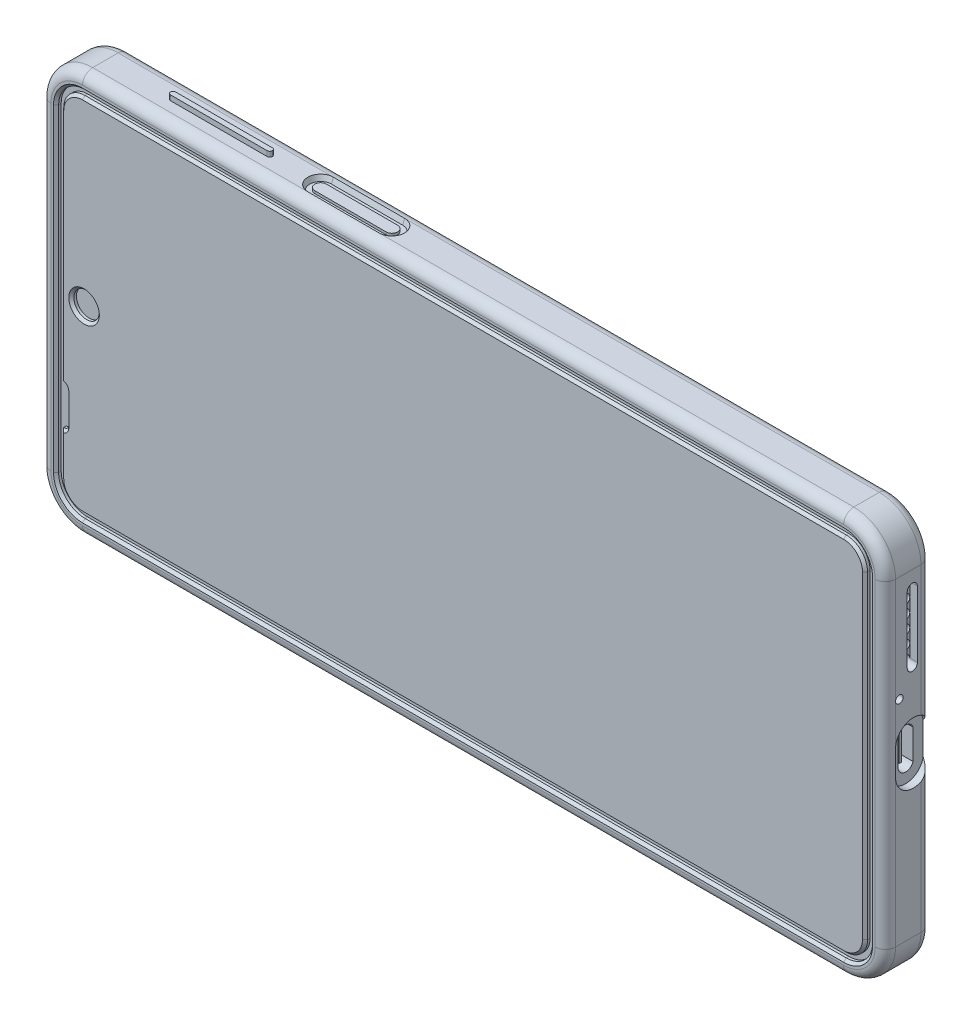
SolidWorks part; units mm, degrees
ref_plane "Front Plane" through (0, 0, 0) normal (0, 0, 1) x (1, 0, 0)
ref_plane "Top Plane" through (0, 0, 0) normal (0, 1, 0) x (1, 0, 0)
ref_plane "Right Plane" through (0, 0, 0) normal (1, 0, 0) x (0, 0, -1)
sketch "Sketch1" plane through (0, 0, 0) normal (0, 0, 1) x (1, 0, 0)
  line L1 (-83, -39.5) -> (83, -39.5)
  line L2 (-83, -39.5) -> (-83, 39.5)
  line L3 (-83, 39.5) -> (83, 39.5)
  line L4 (83, -39.5) -> (83, 39.5)
  line L5 (-83, -39.5) -> (83, 39.5) construction
  line L6 (-83, 39.5) -> (83, -39.5) construction
  point P0 (0, 0)
  dimension "D1" = 79
  dimension "D2" = 166
extrude "Boss-Extrude1" add sketch "Sketch1" along normal blind 9
fillet "Fillet1" radius 2 8 edges at (0, 39.5, 0) (-83, 0, 0) (0, -39.5, 0) (83, 0, 0) (0, -39.5, 9) (-83, 0, 9) (0, 39.5, 9) (83, 0, 9)
fillet "Fillet2" radius 8.2 12 edges at (82.4142, 38.9142, 0.5858) (82.4142, 38.9142, 8.4142) (-82.4142, 38.9142, 0.5858) (-82.4142, 38.9142, 8.4142) (-82.4142, -38.9142, 0.5858) (-82.4142, -38.9142, 8.4142) (82.4142, -38.9142, 0.5858) (82.4142, -38.9142, 8.4142) (83, -39.5, 4.5) (-83, -39.5, 4.5) (-83, 39.5, 4.5) (83, 39.5, 4.5)
sketch "Sketch2" plane through (83, 0, 0) normal (1, 0, 0) x (0, 0, -1)
  line L0 (-3.5, 2.5) -> (-3.5, -2.5) construction
  line L1 (0, 2.5) -> (0, -2.5)
  line L2 (-7, 2.5) -> (-7, -2.5)
  line L3 (0, 31.3) -> (0, -31.3) construction
  line L6 (-3.5, 6) -> (-3.5, 31.3) construction
  line L7 (-2, 31.3) -> (-7, 31.3) construction
  line L8 (-3.5, -6) -> (-3.5, -31.3) construction
  line L9 (-7, -31.3) -> (-2, -31.3) construction
  arc A0 (0, 2.5) -> (-7, 2.5) centre (-3.5, 2.5) ccw
  arc A1 (-7, -2.5) -> (0, -2.5) centre (-3.5, -2.5) ccw
  point P2 (-3.5, 0)
  point P7 (-3.5, 6)
  point P8 (-3.5, -6)
  point P9 (-7, 0)
  point P10 (0, 0)
  dimension "D1" = 12
  dimension "D2" = 7
extrude "Cut-Extrude1" cut sketch "Sketch2" against normal blind 1.5
sketch "Sketch3" plane through (81.5, 0, 0) normal (1, 0, 0) x (0, 0, -1)
  line L4 (-5, 2.5) -> (-5, -2.5)
  line L5 (-2.0635, -2.9318) -> (-2.0635, 2.9318)
  line L6 (-5, 2.5) -> (-5, -2.5)
  line L8 (-2.0635, -2.9318) -> (-2.0635, 2.9318)
  arc A4 (-2.0635, 2.9318) -> (-5, 2.5) centre (-3.5, 2.5) ccw
  arc A5 (-5, -2.5) -> (-2.0635, -2.9318) centre (-3.5, -2.5) ccw
  arc A6 (-2.0635, 2.9318) -> (-5, 2.5) centre (-3.5, 2.5) ccw
  arc A7 (-5, -2.5) -> (-2.0635, -2.9318) centre (-3.5, -2.5) ccw
  dimension "D1" = 2
extrude "Cut-Extrude2" cut sketch "Sketch3" against normal blind 4
sketch "Sketch4" plane through (77.5, 0, 0) normal (1, 0, 0) x (0, 0, -1)
  line L1 (-3.7818, 2.9318) -> (-3.2818, 2.9318)
  line L2 (-3.7818, 2.9318) -> (-3.7818, -2.9318)
  line L3 (-3.7818, -2.9318) -> (-3.2818, -2.9318)
  line L4 (-3.2818, 2.9318) -> (-3.2818, -2.9318)
  line L5 (-3.7818, 2.9318) -> (-3.2818, -2.9318) construction
  line L6 (-3.7818, -2.9318) -> (-3.2818, 2.9318) construction
  line L7 (-2.0635, -2.9318) -> (-2.0635, 2.9318) construction
  line L8 (-2.0635, 0) -> (-3.2818, 0) construction
  line L9 (-3.7818, 0) -> (-5, 0) construction
  line L10 (-5, 2.5) -> (-5, -2.5) construction
  point P0 (-3.5318, 0)
  dimension "D1" = 0.5
extrude "Boss-Extrude2" add sketch "Sketch4" along normal blind 3
sketch "Sketch5" plane through (83, 0, 0) normal (1, 0, 0) x (0, 0, -1)
  line L0 (-3.7, 27.9841) -> (-3.7, 14.9841) construction
  line L1 (-2.7, 27.9841) -> (-2.7, 14.9841)
  line L2 (-4.7, 27.9841) -> (-4.7, 14.9841)
  line L4 (-2, 5.6623) -> (-2, 31.3) construction
  arc A0 (-2.7, 27.9841) -> (-4.7, 27.9841) centre (-3.7, 27.9841) ccw
  arc A1 (-4.7, 14.9841) -> (-2.7, 14.9841) centre (-3.7, 14.9841) ccw
  arc A2 (-0.0635, 3.1637) -> (-7, 2.5) centre (-3.5, 2.5) ccw construction
  point P2 (-3.7, 21.4841)
  point P9 (-3.7, 13.9841)
  point P10 (-3.7, 28.9841)
  point P14 (-3.8334, 5.9841)
  dimension "D1" = 0.7
  dimension "D2" = 15
  dimension "D3" = 2
  dimension "D4" = 8
extrude "Cut-Extrude3" cut sketch "Sketch5" against normal blind 1.5
sketch "Sketch6" plane through (81.5, 0, 0) normal (1, 0, 0) x (0, 0, -1)
  line L0 (-3.7, 27.9841) -> (-3.7, 25.3841) construction
  line L1 (-3.7, 25.3841) -> (-3.7, 22.7841) construction
  line L2 (-3.7, 22.7841) -> (-3.7, 20.1841) construction
  line L3 (-3.7, 20.1841) -> (-3.7, 17.5841) construction
  line L4 (-3.7, 17.5841) -> (-3.7, 14.9841) construction
  circle A0 centre (-3.7, 27.9841) radius 1
  circle A1 centre (-3.7, 25.3841) radius 1
  circle A2 centre (-3.7, 22.7841) radius 1
  circle A3 centre (-3.7, 20.1841) radius 1
  circle A4 centre (-3.7, 17.5841) radius 1
  circle A5 centre (-3.7, 14.9841) radius 1
  arc A6 (-2.7, 27.9841) -> (-4.7, 27.9841) centre (-3.7, 27.9841) ccw construction
  arc A7 (-4.7, 14.9841) -> (-2.7, 14.9841) centre (-3.7, 14.9841) ccw construction
extrude "Cut-Extrude4" cut sketch "Sketch6" against normal blind 4
sketch "Sketch7" plane through (83, 0, 0) normal (1, 0, 0) x (0, 0, -1)
  line L0 (-7, 31.3) -> (-7, 2.5) construction
  circle A0 centre (-6.25, 10.4841) radius 0.75
  circle A1 centre (-3.7, 14.9841) radius 1 construction
  dimension "D1" = 1.5
  dimension "D2" = 4.5
extrude "Cut-Extrude5" cut sketch "Sketch7" against normal blind 1.5
sketch "Sketch8" plane through (0, -39.5, 0) normal (0, -1, 0) x (1, 0, 0)
  line L0 (-42, 4.5) -> (-34.5, 4.5) construction
  line L1 (-42, 5.5) -> (-34.5, 5.5)
  line L2 (-42, 3.5) -> (-34.5, 3.5)
  line L3 (-74.8, 2) -> (74.8, 2) construction
  line L4 (74.8, 7) -> (-74.8, 7) construction
  line L6 (-83, 2) -> (-83, 7) construction
  arc A0 (-42, 5.5) -> (-42, 3.5) centre (-42, 4.5) ccw
  arc A1 (-34.5, 3.5) -> (-34.5, 5.5) centre (-34.5, 4.5) ccw
  point P2 (-38.25, 4.5)
  point P7 (-43, 4.5)
  point P8 (-33.5, 4.5)
  dimension "D1" = 2
  dimension "D2" = 9.5
  dimension "D4" = 40
extrude "Boss-Extrude3" add sketch "Sketch8" along normal blind 1
sketch "Sketch9" plane through (-83, 0, 0) normal (-1, 0, 0) x (0, 0, 1)
  line L0 (7, -31.3) -> (7, 31.3) construction
  line L1 (2, -31.3) -> (7, -31.3) construction
  line L2 (6.25, -26.6) -> (6.25, -31.3) construction
  line L3 (3.5, -39.5) -> (5.5, -39.5) construction
  circle A0 centre (6.25, -25.85) radius 0.75
  dimension "D1" = 1.5
  dimension "D3" = 12.9
extrude "Cut-Extrude6" cut sketch "Sketch9" against normal blind 1.5
sketch "Sketch10" plane through (0, 0, 9) normal (0, 0, 1) x (1, 0, 0)
  line L8 (74.8, 36.5) -> (-74.8, 36.5)
  line L9 (-80, 31.3) -> (-80, -31.3)
  line L10 (-74.8, -36.5) -> (74.8, -36.5)
  line L11 (80, -31.3) -> (80, 31.3)
  line L12 (74.8, 36.5) -> (-74.8, 36.5)
  line L14 (-74.8, -36.5) -> (74.8, -36.5)
  line L15 (80, -31.3) -> (80, 31.3)
  line L24 (-80, -31.3) -> (-80, 31.3)
  line L25 (-79, -31.3) -> (-79, -23.1)
  line L26 (-79, -23.1) -> (-78.9, -23.1)
  line L27 (-78, -22.2) -> (-78, -16)
  line L28 (74.8, 35.5) -> (-74.8, 35.5)
  line L29 (-79, 31.3) -> (-79, -31.3)
  line L30 (-74.8, -35.5) -> (74.8, -35.5)
  line L31 (79, -31.3) -> (79, 31.3)
  line L32 (74.8, 35.5) -> (-74.8, 35.5)
  line L34 (-74.8, -35.5) -> (74.8, -35.5)
  line L35 (79, -31.3) -> (79, 31.3)
  line L36 (-78.9, -15.1) -> (-79, -15.1)
  line L37 (-79, -15.1) -> (-79, 31.3)
  arc A8 (80, 31.3) -> (74.8, 36.5) centre (74.8, 31.3) ccw
  arc A9 (-74.8, 36.5) -> (-80, 31.3) centre (-74.8, 31.3) ccw
  arc A10 (-80, -31.3) -> (-74.8, -36.5) centre (-74.8, -31.3) ccw
  arc A11 (74.8, -36.5) -> (80, -31.3) centre (74.8, -31.3) ccw
  arc A12 (80, 31.3) -> (74.8, 36.5) centre (74.8, 31.3) ccw
  arc A13 (-74.8, 36.5) -> (-80, 31.3) centre (-74.8, 31.3) ccw
  arc A14 (-80, -31.3) -> (-74.8, -36.5) centre (-74.8, -31.3) ccw
  arc A15 (74.8, -36.5) -> (80, -31.3) centre (74.8, -31.3) ccw
  arc A18 (-78, -16) -> (-78.9, -15.1) centre (-78.9, -16) ccw
  arc A19 (-78.9, -23.1) -> (-78, -22.2) centre (-78.9, -22.2) ccw
  arc A22 (79, 31.3) -> (74.8, 35.5) centre (74.8, 31.3) ccw
  arc A23 (-74.8, 35.5) -> (-79, 31.3) centre (-74.8, 31.3) ccw
  arc A24 (-79, -31.3) -> (-74.8, -35.5) centre (-74.8, -31.3) ccw
  arc A25 (74.8, -35.5) -> (79, -31.3) centre (74.8, -31.3) ccw
  arc A26 (79, 31.3) -> (74.8, 35.5) centre (74.8, 31.3) ccw
  arc A27 (-74.8, 35.5) -> (-79, 31.3) centre (-74.8, 31.3) ccw
  arc A28 (-79, -31.3) -> (-74.8, -35.5) centre (-74.8, -31.3) ccw
  arc A29 (74.8, -35.5) -> (79, -31.3) centre (74.8, -31.3) ccw
  point P7 (-78, -15.1)
  point P10 (-78, -23.1)
  dimension "D5" = 0.9
  dimension "D2" = 2
  dimension "D3" = 8
  dimension "D4" = 1
  dimension "D1" = 1
  dimension "D6" = 2
extrude "Cut-Extrude7" cut sketch "Sketch10" against normal blind 1
sketch "Sketch11" plane through (0, 0, 9) normal (0, 0, 1) x (1, 0, 0)
  line L0 (-79, 31.3) -> (-79, -15.1) construction
  line L1 (-74.5, 0) -> (-74.5, 35.5) construction
  line L2 (74.8, 35.5) -> (-74.8, 35.5) construction
  line L3 (-74.5, 0) -> (-74.5, -35.5) construction
  line L4 (-74.8, -35.5) -> (74.8, -35.5) construction
  circle A0 centre (-74.5, 0) radius 2.5
  dimension "D1" = 5
  dimension "D2" = 4.5
extrude "Cut-Extrude8" cut sketch "Sketch11" against normal blind 1
fillet "Fillet4" radius 0.5 21 edges at (78.477, -34.977, 9) (80, 0, 9) (78.477, 34.977, 9) (0, 36.5, 9) (-78.477, 34.977, 9) (-80, 0, 9) (-78.477, -34.977, 9) (0, -36.5, 9) (-79, 8.1, 9) (-77.7698, 34.2698, 9) (0, 35.5, 9) (77.7698, 34.2698, 9) (79, 0, 9) (77.7698, -34.2698, 9) (0, -35.5, 9) (-77.7698, -34.2698, 9) (-79, -27.2, 9) (-78.2636, -22.8364, 9) (-78, -19.1, 9) (-78.2636, -15.3636, 9) (-72, 0, 9) profile chamfer
sketch "Sketch12" plane through (0, 0, 0) normal (0, 0, -1) x (-1, 0, 0)
  line L0 (74.8, 37.5) -> (-74.8, 37.5) construction
  line L1 (32, 5.5) -> (72, 5.5)
  line L2 (27, 10.5) -> (27, 28.5)
  line L3 (32, 33.5) -> (72, 33.5)
  line L4 (77, 10.5) -> (77, 28.5)
  line L5 (27, 5.5) -> (77, 33.5) construction
  line L6 (27, 33.5) -> (77, 5.5) construction
  line L7 (81, -31.3) -> (81, 31.3) construction
  arc A0 (32, 5.5) -> (27, 10.5) centre (32, 10.5) cw
  arc A1 (72, 5.5) -> (77, 10.5) centre (72, 10.5) ccw
  arc A2 (72, 33.5) -> (77, 28.5) centre (72, 28.5) cw
  arc A3 (27, 28.5) -> (32, 33.5) centre (32, 28.5) cw
  point P0 (52, 19.5)
  dimension "D5" = 5
  dimension "D1" = 50
  dimension "D2" = 28
  dimension "D3" = 4
  dimension "D4" = 4
extrude "Boss-Extrude4" add sketch "Sketch12" along normal blind 3
sketch "Sketch13" plane through (0, 0, -3) normal (0, 0, -1) x (-1, 0, 0)
  line L8 (32, 7.5) -> (72, 7.5)
  line L9 (75, 10.5) -> (75, 28.5)
  line L10 (72, 31.5) -> (32, 31.5)
  line L11 (29, 28.5) -> (29, 10.5)
  line L12 (32, 7.5) -> (72, 7.5)
  line L13 (75, 10.5) -> (75, 28.5)
  line L14 (72, 31.5) -> (32, 31.5)
  line L15 (29, 28.5) -> (29, 10.5)
  arc A8 (29, 10.5) -> (32, 7.5) centre (32, 10.5) ccw
  arc A9 (72, 7.5) -> (75, 10.5) centre (72, 10.5) ccw
  arc A10 (75, 28.5) -> (72, 31.5) centre (72, 28.5) ccw
  arc A11 (32, 31.5) -> (29, 28.5) centre (32, 28.5) ccw
  arc A12 (29, 10.5) -> (32, 7.5) centre (32, 10.5) ccw
  arc A13 (72, 7.5) -> (75, 10.5) centre (72, 10.5) ccw
  arc A14 (75, 28.5) -> (72, 31.5) centre (72, 28.5) ccw
  arc A15 (32, 31.5) -> (29, 28.5) centre (32, 28.5) ccw
  dimension "D1" = 2
extrude "Cut-Extrude9" cut sketch "Sketch13" against normal blind 3
fillet "Fillet5" radius 1 8 edges at (-27, 19.5, 0) (-28.4645, 32.0355, 0) (-52, 33.5, 0) (-75.5355, 32.0355, 0) (-77, 19.5, 0) (-75.5355, 6.9645, 0) (-52, 5.5, 0) (-28.4645, 6.9645, 0)
fillet "Fillet6" radius 1 16 edges at (-27, 19.5, -3) (-28.4645, 32.0355, -3) (-52, 33.5, -3) (-75.5355, 32.0355, -3) (-77, 19.5, -3) (-75.5355, 6.9645, -3) (-52, 5.5, -3) (-28.4645, 6.9645, -3) (-74.1213, 8.3787, -3) (-75, 19.5, -3) (-74.1213, 30.6213, -3) (-52, 31.5, -3) (-29.8787, 30.6213, -3) (-29, 19.5, -3) (-29.8787, 8.3787, -3) (-52, 7.5, -3)
sketch "Sketch14" plane through (0, 0, 0) normal (0, 0, -1) x (-1, 0, 0)
  line L0 (72, 31.5) -> (32, 31.5) construction
  line L1 (32, 31.5) -> (72, 31.5)
  line L2 (29, 28.5) -> (29, 18.5)
  line L3 (32, 15.5) -> (72, 15.5)
  line L4 (75, 28.5) -> (75, 18.5)
  line L5 (29, 31.5) -> (75, 15.5) construction
  line L6 (29, 15.5) -> (75, 31.5) construction
  line L7 (29, 28.5) -> (29, 10.5) construction
  line L8 (75, 10.5) -> (75, 28.5) construction
  arc A0 (72, 15.5) -> (75, 18.5) centre (72, 18.5) ccw
  arc A1 (29, 18.5) -> (32, 15.5) centre (32, 18.5) ccw
  arc A2 (72, 31.5) -> (75, 28.5) centre (72, 28.5) cw
  arc A3 (32, 31.5) -> (29, 28.5) centre (32, 28.5) ccw
  point P0 (52, 23.5)
  dimension "D2" = 3
  dimension "D1" = 16
extrude "Boss-Extrude5" add sketch "Sketch14" along normal blind 1
sketch "Sketch15" plane through (0, 0, -1) normal (0, 0, -1) x (-1, 0, 0)
  line L0 (37, 23.5) -> (52, 23.5) construction
  line L1 (52, 23.5) -> (67, 23.5) construction
  line L2 (67, 23.5) -> (75, 23.5) construction
  line L4 (75, 18.5) -> (75, 28.5) construction
  line L5 (37, 23.5) -> (29, 23.5) construction
  line L6 (29, 28.5) -> (29, 18.5) construction
  line L7 (32, 15.5) -> (72, 15.5) construction
  line L8 (72, 31.5) -> (32, 31.5) construction
  circle A0 centre (37, 23.5) radius 6.5
  circle A1 centre (52, 23.5) radius 6.5
  circle A2 centre (67, 23.5) radius 6.5
  dimension "D1" = 13
  dimension "D2" = 15
extrude "Boss-Extrude6" add sketch "Sketch15" along normal blind 1
sketch "Sketch16" plane through (0, 0, 0) normal (0, 0, -1) x (-1, 0, 0)
  line L0 (67, 23.5) -> (67, -1.664) construction
  line L1 (20.1597, 11.5) -> (96.774, 11.5) construction
  line L2 (32, 15.5) -> (72, 15.5) construction
  line L3 (32, 7.5) -> (72, 7.5) construction
  circle A0 centre (67, 12) radius 1
  dimension "D1" = 2
extrude "Cut-Extrude10" cut sketch "Sketch16" against normal blind 0.1
sketch "Sketch17" plane through (0, 0, 0) normal (0, 0, -1) x (-1, 0, 0)
  line L0 (33.5, 11.5) -> (41.5, 11.5) construction
  line L1 (33.5, 13) -> (41.5, 13)
  line L2 (33.5, 10) -> (41.5, 10)
  line L3 (32, 15.5) -> (72, 15.5) construction
  line L4 (32, 7.5) -> (72, 7.5) construction
  line L6 (32, 6.5) -> (32, 16.8974) construction
  arc A0 (33.5, 13) -> (33.5, 10) centre (33.5, 11.5) ccw
  arc A1 (41.5, 10) -> (41.5, 13) centre (41.5, 11.5) ccw
  point P2 (37.5, 11.5)
  dimension "D1" = 3
  dimension "D2" = 8
extrude "Cut-Extrude11" cut sketch "Sketch17" against normal blind 0.1
sketch "Sketch18" plane through (0, 39.5, 0) normal (0, 1, 0) x (1, 0, 0)
  line L0 (-61.5, -4.5) -> (-42.5, -4.5) construction
  line L1 (-61.5, -4) -> (-42.5, -4)
  line L2 (-61.5, -5) -> (-42.5, -5)
  line L4 (-74.8, -7) -> (74.8, -7) construction
  line L5 (74.8, -2) -> (-74.8, -2) construction
  line L6 (-83, -7) -> (-83, -2) construction
  arc A0 (-61.5, -4) -> (-61.5, -5) centre (-61.5, -4.5) ccw
  arc A1 (-42.5, -5) -> (-42.5, -4) centre (-42.5, -4.5) ccw
  point P2 (-52, -4.5)
  point P7 (-62, -4.5)
  point P8 (-42, -4.5)
  dimension "D1" = 20
  dimension "D2" = 1
  dimension "D4" = 21
extrude "Boss-Extrude7" add sketch "Sketch18" along normal blind 1
sketch "Sketch19" plane through (0, 39.5, 0) normal (0, 1, 0) x (1, 0, 0)
  line L0 (-32.5, -4.5) -> (-18.5, -4.5) construction
  line L1 (-32.5, -2) -> (-18.5, -2)
  line L2 (-32.5, -7) -> (-18.5, -7)
  line L3 (74.8, -2) -> (-74.8, -2) construction
  line L4 (-74.8, -7) -> (74.8, -7) construction
  arc A0 (-32.5, -2) -> (-32.5, -7) centre (-32.5, -4.5) ccw
  arc A1 (-18.5, -7) -> (-18.5, -2) centre (-18.5, -4.5) ccw
  arc A2 (-42.5, -5) -> (-42.5, -4) centre (-42.5, -4.5) ccw construction
  point P2 (-25.5, -4.5)
  point P7 (-35, -4.5)
  point P8 (-16, -4.5)
  point P17 (-42, -4.5)
  dimension "D1" = 19
  dimension "D2" = 7
extrude "Cut-Extrude12" cut sketch "Sketch19" against normal blind 1 draft 20
sketch "Sketch20" plane through (0, 38.5, 0) normal (0, 1, 0) x (1, 0, 0)
  line L6 (-32.5, -5.636) -> (-18.5, -5.636)
  line L7 (-18.5, -3.364) -> (-32.5, -3.364)
  line L8 (-32.5, -5.636) -> (-18.5, -5.636)
  line L9 (-18.5, -3.364) -> (-32.5, -3.364)
  arc A6 (-32.5, -3.364) -> (-32.5, -5.636) centre (-32.5, -4.5) ccw
  arc A7 (-18.5, -5.636) -> (-18.5, -3.364) centre (-18.5, -4.5) ccw
  arc A8 (-32.5, -3.364) -> (-32.5, -5.636) centre (-32.5, -4.5) ccw
  arc A9 (-18.5, -5.636) -> (-18.5, -3.364) centre (-18.5, -4.5) ccw
  dimension "D1" = 1
extrude "Boss-Extrude8" add sketch "Sketch20" along normal blind 0.5
